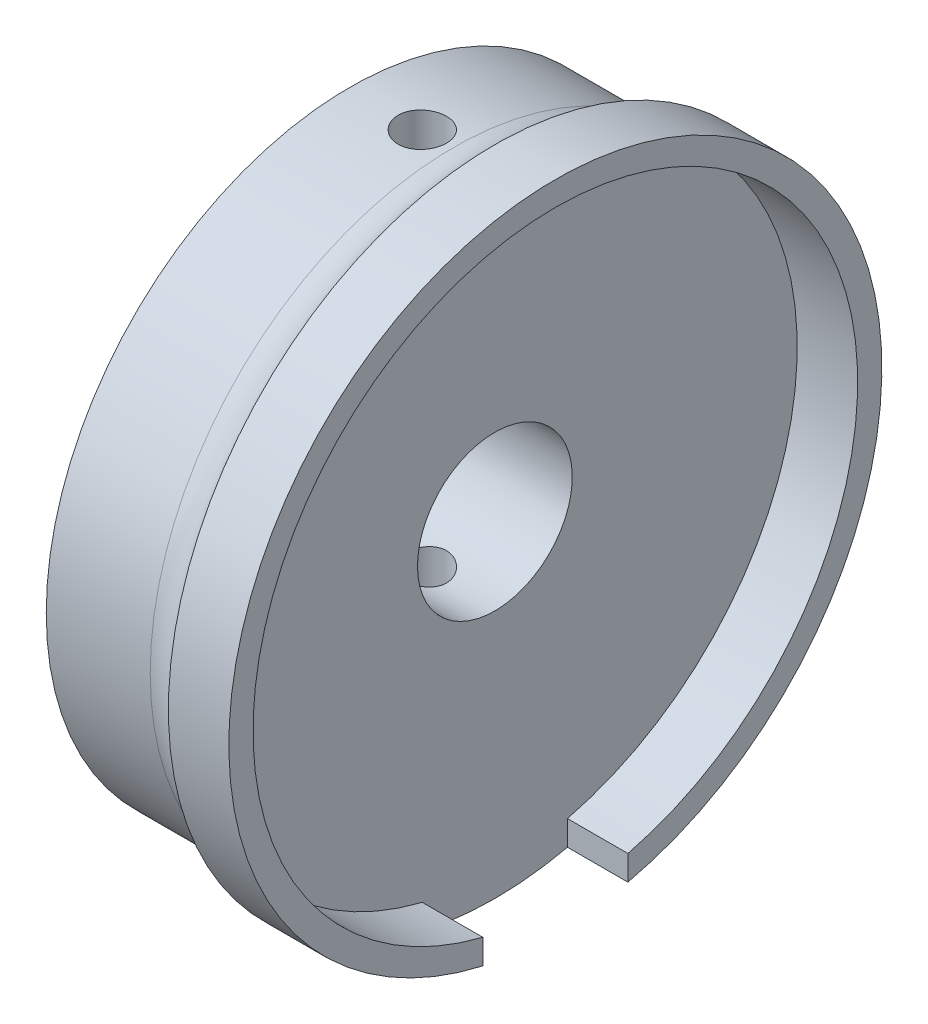
SolidWorks part; units mm, degrees
ref_plane "前视基准面" through (0, 0, 0) normal (0, 0, 1) x (1, 0, 0)
ref_plane "上视基准面" through (0, 0, 0) normal (0, 1, 0) x (1, 0, 0)
ref_plane "右视基准面" through (0, 0, 0) normal (1, 0, 0) x (0, 0, -1)
other "Configuration Table"
sketch "草图1" plane through (0, 0, 0) normal (1, 0, 0) x (0, 0, -1)
  circle A0 centre (0, 0) radius 12.55
  dimension "D1" = 25.1
extrude "凸台-拉伸1" add sketch "草图1" along normal blind 6
sketch "草图2" plane through (0, 0, 0) normal (-1, 0, 0) x (0, 0, 1)
  circle A0 centre (0, 0) radius 3.2
  dimension "D1" = 6.4
extrude "切除-拉伸1" cut sketch "草图2" against normal blind 6
sketch "草图3" plane through (0, 0, 0) normal (0, 1, 0) x (1, 0, 0)
  line L0 (0, 12.55) -> (0, -12.55) construction
  circle A0 centre (3, 0) radius 1
  dimension "D1" = 2
  dimension "D2" = 3
extrude "切除-拉伸2" cut sketch "草图3" against normal up to next and the other way up to next
sketch "草图4" plane through (6, 0, 0) normal (1, 0, 0) x (0, 0, -1)
  circle A0 centre (0, 0) radius 13.5
  dimension "D1" = 27
extrude "凸台-拉伸2" add sketch "草图4" along normal blind 2.5
sketch "草图5" plane through (8.5, 0, 0) normal (1, 0, 0) x (0, 0, -1)
  circle A0 centre (0, 0) radius 12.5
  dimension "D1" = 25
extrude "切除-拉伸3" cut sketch "草图5" against normal blind 2.5
fillet "圆角2" radius 2 1 edges at (6, 0, -12.55)
sketch "草图6" plane through (0, 0, 0) normal (0, 1, 0) x (1, 0, 0)
  line L0 (0, 0) -> (8.5, 0) construction
  line L1 (0, 12.55) -> (0, -12.55) construction
  line L2 (8.5, -13.5) -> (8.5, 13.5) construction
  line L3 (6, 13.5) -> (6, -13.5) construction
  line L4 (6, 3) -> (8.5, 3)
  line L5 (6, 3) -> (6, -3)
  line L6 (6, -3) -> (8.5, -3)
  line L7 (8.5, 3) -> (8.5, -3)
  dimension "D1" = 6
  dimension "D2" = 3
extrude "切除-拉伸4" cut sketch "草图6" against normal blind 15
